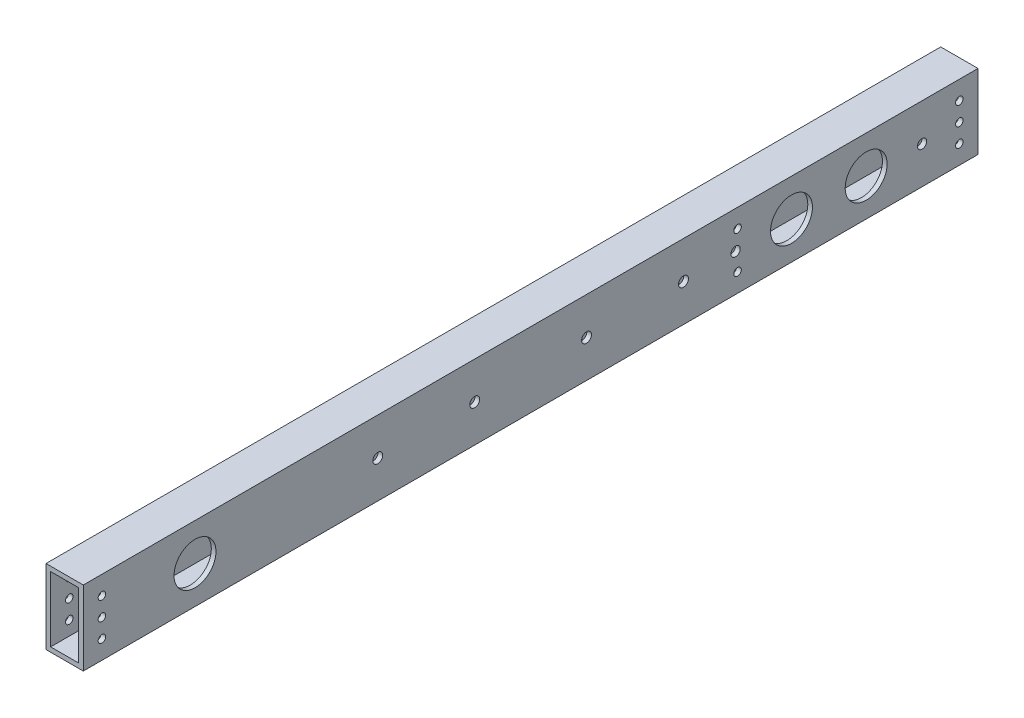
SolidWorks part; units mm, degrees
material "6061-T6 (SS)"
ref_plane "Front Plane" through (0, 0, 0) normal (0, 0, 1) x (1, 0, 0)
ref_plane "Top Plane" through (0, 0, 0) normal (0, 1, 0) x (1, 0, 0)
ref_plane "Right Plane" through (0, 0, 0) normal (1, 0, 0) x (0, 0, -1)
sketch "Sketch1" plane through (0, 0, 0) normal (0, 0, 1) x (1, 0, 0)
  line L0 (-9.525, 22.225) -> (9.525, 22.225)
  line L1 (-12.7, 25.4) -> (12.7, 25.4)
  line L2 (-12.7, 25.4) -> (-12.7, -25.4)
  line L3 (-12.7, -25.4) -> (12.7, -25.4)
  line L4 (12.7, 25.4) -> (12.7, -25.4)
  line L5 (-12.7, 25.4) -> (12.7, -25.4) construction
  line L6 (-12.7, -25.4) -> (12.7, 25.4) construction
  line L7 (9.525, 22.225) -> (9.525, -22.225)
  line L8 (-9.525, -22.225) -> (9.525, -22.225)
  line L9 (-9.525, 22.225) -> (-9.525, -22.225)
  point P0 (0, 0)
  dimension "D1" = 50.8
  dimension "D2" = 25.4
  dimension "D3" = 3.175
extrude "Boss-Extrude1" add sketch "Sketch1" along normal mid plane 609.6
hole_wizard "#10 Clearance Hole1" positions "Sketch4" profile "Sketch3" hole size "#10" standard "ANSI Inch" end condition through all
sketch "Sketch4" plane through (12.7, 0, 0) normal (1, 0, 0) x (0, 0, -1)
  line L0 (-304.8, 25.4) -> (304.8, 25.4) construction
  line L1 (-304.8, -25.4) -> (-304.8, 25.4) construction
  point P0 (-292.1, 12.7)
  point P13 (-292.1, 0)
  point P14 (-292.1, -12.7)
  dimension "D2" = 12.7
  dimension "D3" = 12.7
  dimension "D1" = 3
sketch "Sketch3" plane through (12.7, 12.7, 292.1) normal (0, 1, 0) x (0, 0, -1)
  line L0 (0, 0) -> (0, 25.4)
  line L1 (0, 25.4) -> (2.5527, 25.4)
  line L2 (2.5527, 25.4) -> (2.5527, 0)
  line L5 (2.5527, 0) -> (0, 0)
  line L11 (0, -6.35) -> (0, 107.95) construction
  dimension "Thru Hole Dia." = 5.1054
  dimension "Thru Hole Depth" = 25.4
mirror "Mirror1" about plane through (0, 0, 0) normal (0, 0, 1) of "#10 Clearance Hole1"
hole_wizard "1/4 Clearance Hole2" positions "Sketch6" profile "Sketch5" hole size "1/4" standard "ANSI Inch" end condition through all
sketch "Sketch6" plane through (12.7, 0, 0) normal (1, 0, 0) x (0, 0, -1)
  line L0 (-38.1, 0) -> (38.1, 0) construction
  point P0 (-38.1, 0)
  point P2 (38.1, 0)
  point P13 (-104.14, 0)
  point P15 (104.14, 0)
  dimension "D1" = 76.2
  dimension "D2" = 66.04
  dimension "D3" = 66.04
sketch "Sketch5" plane through (12.7, 0, 38.1) normal (0, 1, 0) x (0, 0, -1)
  line L0 (0, 0) -> (0, 25.4)
  line L1 (0, 25.4) -> (3.3782, 25.4)
  line L2 (3.3782, 25.4) -> (3.3782, 0)
  line L5 (3.3782, 0) -> (0, 0)
  line L11 (0, -6.35) -> (0, 107.95) construction
  dimension "Thru Hole Dia." = 6.7564
  dimension "Thru Hole Depth" = 25.4
sketch "Sketch7" plane through (12.7, 0, 0) normal (1, 0, 0) x (0, 0, -1)
  line L0 (304.8, -25.4) -> (304.8, 25.4) construction
  line L2 (139.6238, 0) -> (266.7, 0) construction
  line L3 (279.4, -25.4) -> (279.4, 25.4) construction
  line L4 (-304.8, -25.4) -> (304.8, -25.4) construction
  line L5 (-304.8, 25.4) -> (304.8, 25.4) construction
  circle A0 centre (-228.6762, 0) radius 14.2875
  circle A1 centre (177.7238, 0) radius 14.2875
  circle A2 centre (228.6, 0) radius 14.2875
  circle A3 centre (177.7238, 0) radius 26.67 construction
  circle A4 centre (228.6, 0) radius 26.67 construction
  circle A5 centre (139.6238, 0) radius 3.175
  circle A6 centre (266.7, 0) radius 3.175
  circle A7 centre (139.6238, 0) radius 6.35 construction
  dimension "D1" = 28.575
  dimension "D2" = 28.575
  dimension "D7" = 53.34
  dimension "D8" = 6.35
  dimension "D12" = 12.7
  dimension "D5" = 406.4
  dimension "D3" = 50.8762
  dimension "D4" = 76.2
  dimension "D9" = 38.1
  dimension "D10" = 38.1
  dimension "D11" = 127.0762
  dimension "D13" = 25.4
extrude "Cut-Extrude1" cut sketch "Sketch7" against normal through all
sketch "Sketch8" plane through (12.7, 0, 0) normal (1, 0, 0) x (0, 0, -1)
  line L0 (-304.8, 25.4) -> (304.8, 25.4) construction
  line L1 (304.8, -25.4) -> (304.8, 25.4) construction
  circle A0 centre (140.97, 12.7) radius 2.5527
  circle A1 centre (140.97, -12.7) radius 2.5527
  dimension "D4" = 5.1054
  dimension "D5" = 5.1054
  dimension "D1" = 25.4
  dimension "D2" = 12.7
  dimension "D3" = 163.83
extrude "Cut-Extrude2" cut sketch "Sketch8" against normal through all
